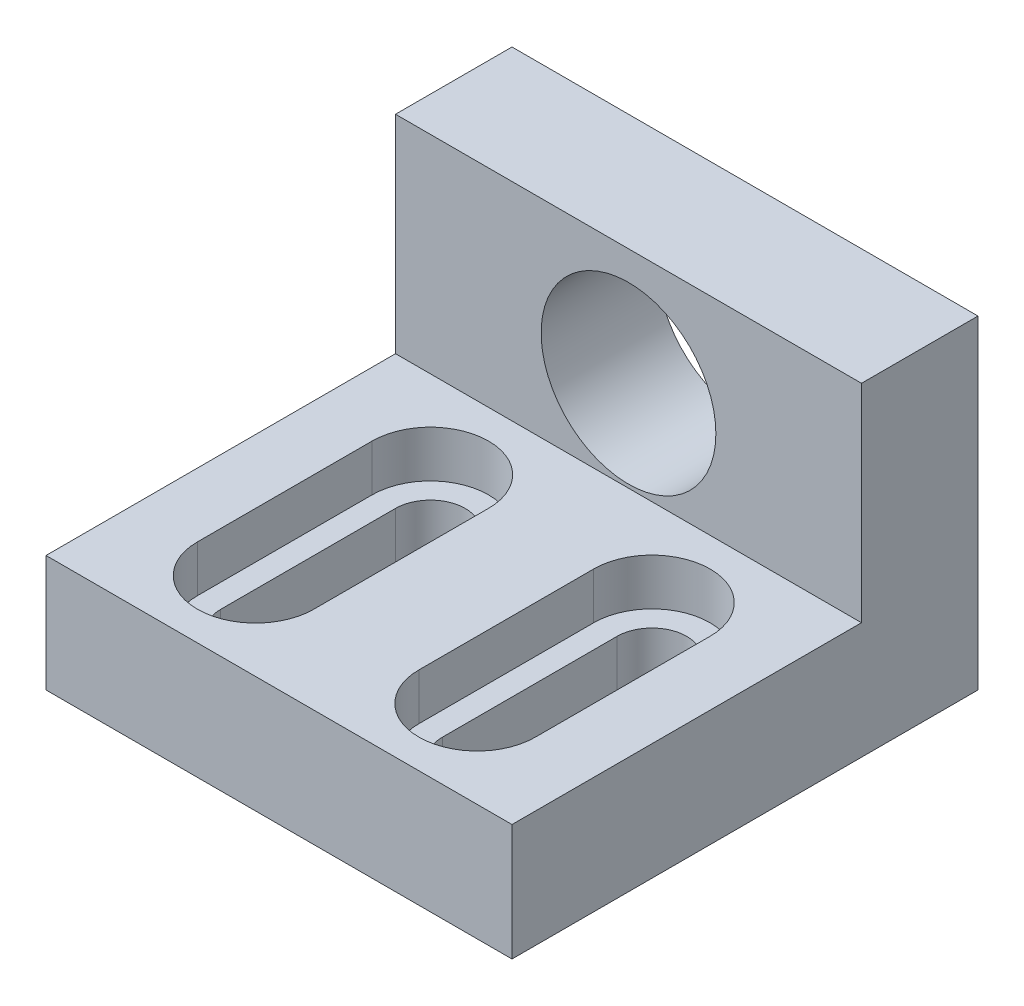
SolidWorks part; units mm, degrees
ref_plane "Front Plane" through (0, 0, 0) normal (0, 0, 1) x (1, 0, 0)
ref_plane "Top Plane" through (0, 0, 0) normal (0, 1, 0) x (1, 0, 0)
ref_plane "Right Plane" through (0, 0, 0) normal (1, 0, 0) x (0, 0, -1)
sketch "Sketch1" plane through (0, 0, 0) normal (0, 0, 1) x (1, 0, 0)
  line L0 (-12.7, 0) -> (-12.7, -11.303)
  line L1 (-12.7, -11.303) -> (12.7, -11.303)
  line L2 (12.7, -11.303) -> (12.7, 0)
  line L3 (-12.7, 0) -> (-12.7, 6.35)
  line L4 (-12.7, 6.35) -> (12.7, 6.35)
  line L5 (12.7, 6.35) -> (12.7, 0)
  circle A1 centre (0, 0) radius 4.7625
  dimension "D1" = 6.35
  dimension "D2" = 9.525
  dimension "D3" = 11.303
  dimension "D4" = 25.4
  dimension "D5" = 12.7
extrude "Boss-Extrude1" add sketch "Sketch1" along normal blind 6.35
sketch "Sketch2" plane through (0, 0, 6.35) normal (0, 0, 1) x (1, 0, 0)
  line L0 (12.7, -11.303) -> (12.7, 6.35) construction
  line L1 (-12.7, -11.303) -> (12.7, -11.303)
  line L2 (-12.7, -11.303) -> (-12.7, -4.953)
  line L3 (-12.7, -4.953) -> (12.7, -4.953)
  line L4 (12.7, -11.303) -> (12.7, -4.953)
  dimension "D1" = 6.35
extrude "Boss-Extrude2" add sketch "Sketch2" along normal blind 19.05
sketch "Sketch8" plane through (0, -4.953, 0) normal (0, 1, 0) x (1, 0, 0)
  line L2 (-7.9375, -11.1125) -> (-7.9375, -20.6375)
  line L4 (-4.1402, -11.1125) -> (-4.1402, -20.6375)
  line L6 (4.1402, -11.1125) -> (4.1402, -20.6375)
  line L8 (7.9375, -11.1125) -> (7.9375, -20.6375)
  line L9 (-12.7, -25.4) -> (-12.7, -6.35) construction
  line L10 (12.7, -25.4) -> (12.7, -6.35) construction
  line L15 (2.8638, -20.6375) -> (2.8638, -11.1125)
  line L17 (9.2138, -20.6375) -> (9.2138, -11.1125)
  line L19 (-9.2139, -11.1125) -> (-9.2139, -20.6375)
  line L21 (-2.8639, -11.1125) -> (-2.8639, -20.6375)
  arc A0 (-7.9375, -20.6375) -> (-4.1402, -20.6375) centre (-6.0389, -20.6375) ccw
  arc A1 (-4.1402, -11.1125) -> (-7.9375, -11.1125) centre (-6.0389, -11.1125) ccw
  arc A2 (7.9375, -11.1125) -> (4.1402, -11.1125) centre (6.0388, -11.1125) ccw
  arc A3 (4.1402, -20.6375) -> (7.9375, -20.6375) centre (6.0388, -20.6375) ccw
  arc A4 (-2.8639, -11.1125) -> (-9.2139, -11.1125) centre (-6.0389, -11.1125) ccw
  arc A5 (-9.2139, -20.6375) -> (-2.8639, -20.6375) centre (-6.0389, -20.6375) ccw
  arc A6 (9.2138, -11.1125) -> (2.8638, -11.1125) centre (6.0388, -11.1125) ccw
  arc A7 (2.8638, -20.6375) -> (9.2138, -20.6375) centre (6.0388, -20.6375) ccw
  dimension "D9" = 6.35
  dimension "D10" = 6.35
  dimension "D11" = 6.35
  dimension "D12" = 6.35
  dimension "D1" = 3.7973
  dimension "D2" = 3.7973
  dimension "D3" = 4.7625
  dimension "D4" = 4.7625
extrude "Cut-Extrude6" cut sketch "Sketch8" against normal through all contours L4 A1 L2 A0 | L6 A3 L8 A2 region at (-6.0389, -4.953, 15.875) region at (6.0388, -4.953, 15.875)
extrude "Cut-Extrude7" cut sketch "Sketch8<10>" against normal blind 2.54
sketch "Sketch8<10>" plane through (0, -4.953, 0) normal (0, 1, 0) x (1, 0, 0) same geometry as "Sketch8"
